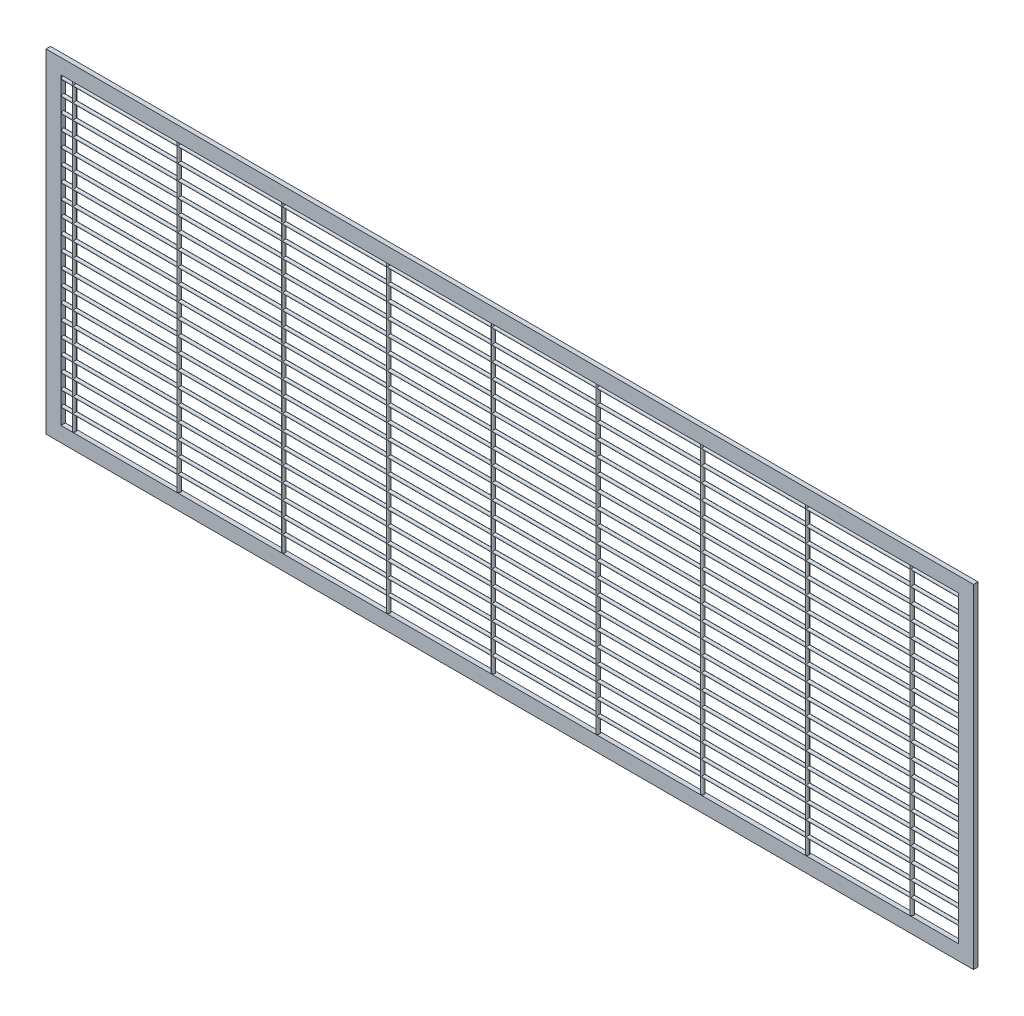
SolidWorks part; units mm, degrees
ref_plane "Front Plane" through (0, 0, 0) normal (0, 0, 1) x (1, 0, 0)
ref_plane "Top Plane" through (0, 0, 0) normal (0, 1, 0) x (1, 0, 0)
ref_plane "Right Plane" through (0, 0, 0) normal (1, 0, 0) x (0, 0, -1)
sketch "Sketch1" plane through (0, 0, 0) normal (0, 0, 1) x (1, 0, 0)
  line L1 (0, 0) -> (620, 0)
  line L2 (0, 0) -> (0, 223)
  line L3 (0, 223) -> (620, 223)
  line L4 (620, 0) -> (620, 223)
  line L5 (10, 10) -> (610, 10)
  line L6 (10, 10) -> (10, 213)
  line L7 (10, 213) -> (610, 213)
  line L8 (610, 10) -> (610, 213)
  dimension "D1" = 223
  dimension "D2" = 620
  dimension "D3" = 10
  dimension "D4" = 10
  dimension "D5" = 10
  dimension "D6" = 10
extrude "Boss-Extrude1" add sketch "Sketch1" along normal blind 3
sketch "Sketch2" plane through (610, 0, 0) normal (-1, 0, 0) x (0, 0, 1)
  line L0 (3, 223) -> (3, 0) construction
  circle A0 centre (1.5, 210.4593) radius 1.022
  circle A1 centre (1.5, 200.4593) radius 1.022
  circle A2 centre (1.5, 190.4593) radius 1.022
  circle A3 centre (1.5, 180.4593) radius 1.022
  circle A4 centre (1.5, 170.4593) radius 1.022
  circle A5 centre (1.5, 160.4593) radius 1.022
  circle A6 centre (1.5, 150.4593) radius 1.022
  circle A7 centre (1.5, 140.4593) radius 1.022
  circle A8 centre (1.5, 130.4593) radius 1.022
  circle A9 centre (1.5, 120.4593) radius 1.022
  circle A10 centre (1.5, 110.4593) radius 1.022
  circle A11 centre (1.5, 100.4593) radius 1.022
  circle A12 centre (1.5, 90.4593) radius 1.022
  circle A13 centre (1.5, 80.4593) radius 1.022
  circle A14 centre (1.5, 70.4593) radius 1.022
  circle A15 centre (1.5, 60.4593) radius 1.022
  circle A16 centre (1.5, 50.4593) radius 1.022
  circle A17 centre (1.5, 40.4593) radius 1.022
  circle A18 centre (1.5, 30.4593) radius 1.022
  circle A19 centre (1.5, 20.4593) radius 1.022
  circle A22 centre (1.5, 10.4593) radius 1.022 [skipped]
  circle A23 centre (1.5, 0.4593) radius 1.022 [skipped]
  dimension "D1" = 1.5
  dimension "D2" = 22
extrude "Boss-Extrude2" add sketch "Sketch2" along normal blind 600
sketch "Sketch3" plane through (0, 10, 0) normal (0, 1, 0) x (1, 0, 0)
  line L0 (620, 0) -> (0, 0) construction
  circle A0 centre (17.5794, -1.5) radius 1.0648
  circle A1 centre (87.5794, -1.5) radius 1.0648
  circle A2 centre (157.5794, -1.5) radius 1.0648
  circle A3 centre (227.5794, -1.5) radius 1.0648
  circle A4 centre (297.5794, -1.5) radius 1.0648
  circle A5 centre (367.5794, -1.5) radius 1.0648
  circle A6 centre (437.5794, -1.5) radius 1.0648
  circle A7 centre (507.5794, -1.5) radius 1.0648
  circle A8 centre (577.5794, -1.5) radius 1.0648
  dimension "D1" = 1.5
  dimension "D2" = 9
extrude "Boss-Extrude3" add sketch "Sketch3" along normal blind 203
